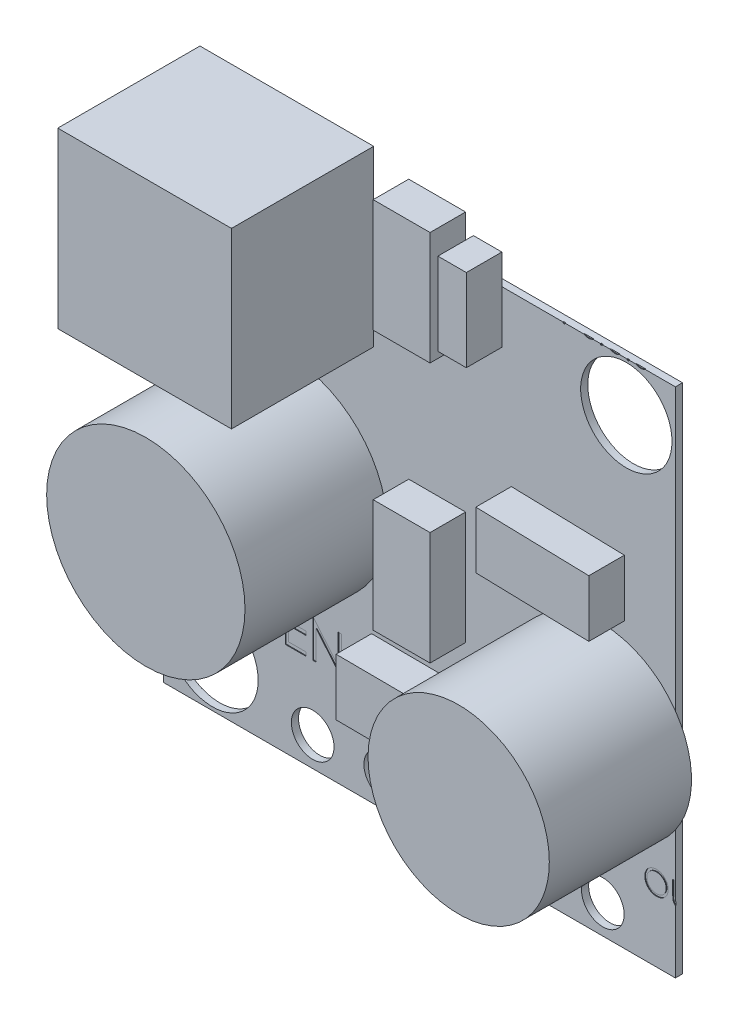
SolidWorks part; units mm, degrees
ref_plane "Front Plane" through (0, 0, 0) normal (0, 0, 1) x (1, 0, 0)
ref_plane "Top Plane" through (0, 0, 0) normal (0, 1, 0) x (1, 0, 0)
ref_plane "Right Plane" through (0, 0, 0) normal (1, 0, 0) x (0, 0, -1)
sketch "Sketch1" plane through (0, 0, 0) normal (0, 0, 1) x (1, 0, 0)
  line L0 (0.669, -0.5811) -> (0.669, 1.1715) construction
  line L1 (-1.0836, -0.5811) -> (17.2082, -0.5811)
  line L2 (-1.0836, -0.5811) -> (-1.0836, 17.7107)
  line L3 (-1.0836, 17.7107) -> (17.2082, 17.7107)
  line L4 (17.2082, -0.5811) -> (17.2082, 17.7107)
  line L5 (0.669, 1.1715) -> (-1.0836, 1.1715) construction
  line L6 (15.4556, 17.7107) -> (15.4556, 15.9581) construction
  line L7 (15.4556, 15.9581) -> (17.2082, 15.9581) construction
  line L8 (-1.0836, 0.4655) -> (4.2504, 0.4655) construction
  line L9 (4.2504, 0.4655) -> (6.8419, 0.4655) construction
  line L10 (6.8419, 0.4655) -> (9.4335, 0.4655) construction
  line L11 (9.4335, 0.4655) -> (12.0251, 0.4655) construction
  line L12 (12.0251, 0.4655) -> (14.6166, 0.4655) construction
  line L13 (14.6166, 0.4655) -> (17.2082, 0.4655) construction
  circle A0 centre (0.669, 1.1715) radius 1.632
  circle A1 centre (15.4556, 15.9581) radius 1.632
  circle A2 centre (4.2504, 0.4655) radius 0.762
  circle A3 centre (6.8419, 0.4655) radius 0.762
  circle A4 centre (9.4335, 0.4655) radius 0.762
  circle A5 centre (12.0251, 0.4655) radius 0.762
  circle A6 centre (14.6166, 0.4655) radius 0.762
  dimension "D1" = 3.2639
  dimension "D2" = 20.9115
extrude "Boss-Extrude2" add sketch "Sketch1" along normal blind 0.254
sketch "Sketch2" plane through (0, 0, 0.254) normal (0, 0, 1) x (1, 0, 0)
  line L0 (17.2082, 17.7107) -> (-1.0836, 17.7107) construction
  line L1 (0.2217, 19.7636) -> (6.428, 19.7636)
  line L2 (0.2217, 19.7636) -> (0.2217, 13.5573)
  line L3 (0.2217, 13.5573) -> (6.428, 13.5573)
  line L4 (6.428, 19.7636) -> (6.428, 13.5573)
  circle A0 centre (3.3674, 8.2222) radius 3.5433
  circle A1 centre (14.5452, 5.8421) radius 3.2385
extrude "Boss-Extrude3" add sketch "Sketch2" along normal blind 5.08
sketch "Sketch3" plane through (0, 0, 0.254) normal (0, 0, 1) x (1, 0, 0)
  line L1 (6.3544, 4.6463) -> (10.3929, 4.6203)
  line L2 (6.3544, 4.6463) -> (6.3545, 2.6143)
  line L3 (6.3545, 2.6143) -> (10.393, 2.5883)
  line L4 (10.3929, 4.6203) -> (10.393, 2.5883)
  line L5 (7.6807, 10.0893) -> (9.7127, 10.0893)
  line L6 (7.6807, 10.0893) -> (7.6807, 6.0507)
  line L7 (7.6807, 6.0507) -> (9.7127, 6.0507)
  line L8 (9.7127, 10.0893) -> (9.7127, 6.0507)
  line L9 (7.6807, 19.3736) -> (9.7127, 19.3736)
  line L10 (7.6807, 19.3736) -> (7.6807, 15.335)
  line L11 (7.6807, 15.335) -> (9.7127, 15.335)
  line L12 (9.7127, 19.3736) -> (9.7127, 15.335)
  line L13 (11.3476, 11.6941) -> (15.3849, 11.59)
  line L14 (11.3476, 11.6941) -> (11.3498, 9.6621)
  line L15 (11.3498, 9.6621) -> (15.3871, 9.558)
  line L16 (15.3849, 11.59) -> (15.3871, 9.558)
  line L17 (9.9933, 18.7829) -> (11.0093, 18.7829)
  line L18 (9.9933, 18.7829) -> (9.9933, 15.8365)
  line L19 (9.9933, 15.8365) -> (11.0093, 15.8365)
  line L20 (11.0093, 18.7829) -> (11.0093, 15.8365)
extrude "Boss-Extrude4" add sketch "Sketch3" along normal blind 1.27
sketch "Sketch4" plane through (0, 0, 0.254) normal (0, 0, 1) x (1, 0, 0)
  line L0 (13.09, 17.6755) -> (16.0548, 17.6755) construction
  line L1 (3.1036, 2.7739) -> (4.2739, 2.7739) construction
  line L2 (7.0305, 1.6296) -> (8.0968, 1.6296) construction
  line L3 (10.3594, 1.6296) -> (12.3098, 1.6296) construction
  line L4 (16.0548, 1.6296) -> (18.4734, 1.6296) construction
  text T0 "Pololu" font "Century Gothic" height in points 3
  text T1 "EN" font "Century Gothic" height in points 5
  text T2 "VIN" font "Century Gothic" height in points 3
  text T3 "GND" font "Century Gothic" height in points 3
  text T4 "OUT" font "Century Gothic" height in points 3
extrude "Cut-Extrude1" cut sketch "Sketch4" against normal blind 0.0254
